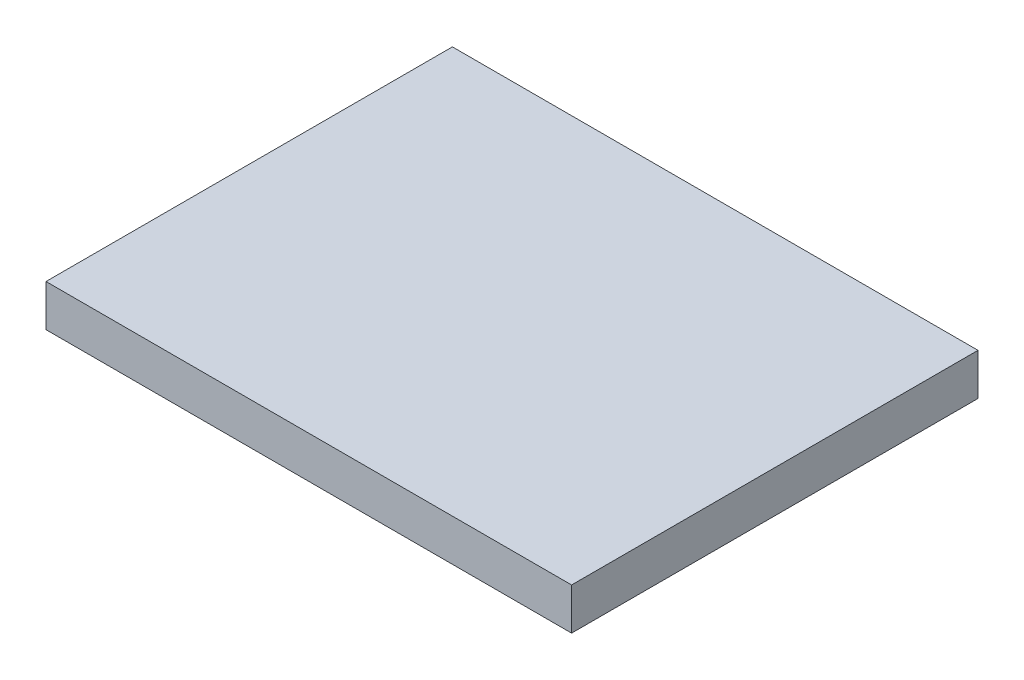
SolidWorks part; units mm, degrees
ref_plane "Front Plane" through (0, 0, 0) normal (0, 0, 1) x (1, 0, 0)
ref_plane "Top Plane" through (0, 0, 0) normal (0, 1, 0) x (1, 0, 0)
ref_plane "Right Plane" through (0, 0, 0) normal (1, 0, 0) x (0, 0, -1)
sketch "Sketch1" plane through (0, 0, 0) normal (0, 1, 0) x (1, 0, 0)
  line L1 (0, 0) -> (125.9603, 0)
  line L2 (0, 0) -> (0, 97.3933)
  line L3 (0, 97.3933) -> (125.9603, 97.3933)
  line L4 (125.9603, 0) -> (125.9603, 97.3933)
extrude "Boss-Extrude1" add sketch "Sketch1" along normal blind 10
